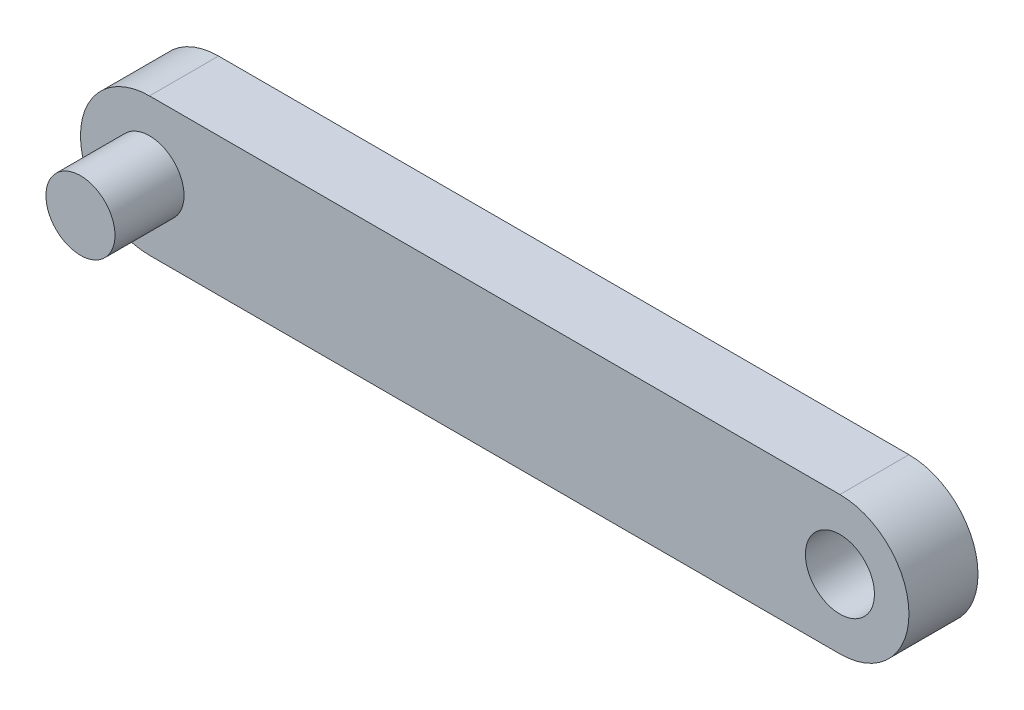
SolidWorks part; units mm, degrees
ref_plane "Front Plane" through (0, 0, 0) normal (0, 0, 1) x (1, 0, 0)
ref_plane "Top Plane" through (0, 0, 0) normal (0, 1, 0) x (1, 0, 0)
ref_plane "Right Plane" through (0, 0, 0) normal (1, 0, 0) x (0, 0, -1)
sketch "Sketch1" plane through (0, 0, 0) normal (0, 0, 1) x (1, 0, 0)
  line L0 (-25, 0) -> (25, 0) construction
  line L1 (-25, 5) -> (25, 5)
  line L2 (-25, -5) -> (25, -5)
  arc A0 (-25, 5) -> (-25, -5) centre (-25, 0) ccw
  arc A1 (25, -5) -> (25, 5) centre (25, 0) ccw
  circle A2 centre (-25, 0) radius 2.5
  circle A3 centre (25, 0) radius 2.5
  point P2 (0, 0)
  dimension "D1" = 5
  dimension "D2" = 5
  dimension "D3" = 50
extrude "Boss-Extrude1" add sketch "Sketch1" along normal blind 5
extrude "Boss-Extrude2" add sketch "Sketch1<2>" along normal blind 10 contours A2 region at (-25, 0, 0)
sketch "Sketch1<2>" plane through (0, 0, 0) normal (0, 0, 1) x (1, 0, 0) same geometry as "Sketch1"
